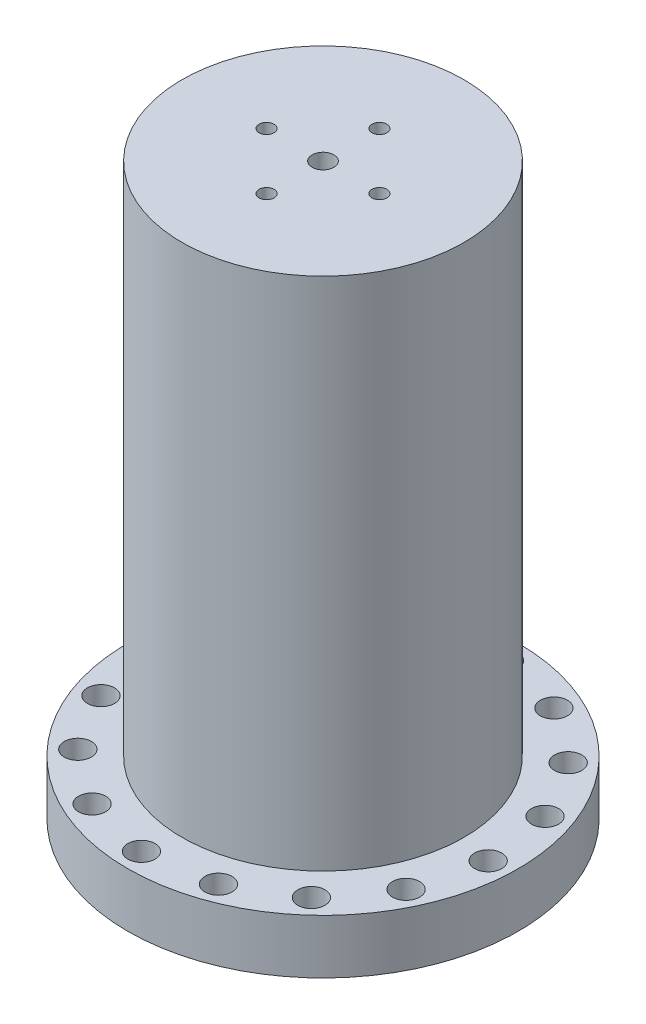
SolidWorks part; units mm, degrees
ref_plane "Front Plane" through (0, 0, 0) normal (0, 0, 1) x (1, 0, 0)
ref_plane "Top Plane" through (0, 0, 0) normal (0, 1, 0) x (1, 0, 0)
ref_plane "Right Plane" through (0, 0, 0) normal (1, 0, 0) x (0, 0, -1)
sketch "Sketch1" plane through (0, 0, 0) normal (0, 1, 0) x (1, 0, 0)
  circle A0 centre (0, 0) radius 45.72
extrude "Boss-Extrude1" add sketch "Sketch1" along normal blind 12.7
sketch "Sketch2" plane through (0, 12.7, 0) normal (0, 1, 0) x (1, 0, 0)
  circle A0 centre (0, 0) radius 33.02
extrude "Boss-Extrude2" add sketch "Sketch2" along normal blind 120.65
sketch "Sketch3" plane through (0, 0, 0) normal (0, -1, 0) x (1, 0, 0)
  circle A0 centre (0, 0) radius 25.4
extrude "Cut-Extrude1" cut sketch "Sketch3" against normal blind 128.27 contours A0
sketch "Sketch4" plane through (0, 133.35, 0) normal (0, 1, 0) x (1, 0, 0)
  circle A0 centre (0, 0) radius 2.54
extrude "Cut-Extrude2" cut sketch "Sketch4" against normal blind 128.27
sketch "Sketch5" plane through (0, 0, 0) normal (0, -1, 0) x (1, 0, 0)
  circle A0 centre (0, 0) radius 40.64
  circle A1 centre (-13.7597, -38.2398) radius 3.175
extrude "Cut-Extrude3" cut sketch "Sketch5" against normal blind 128.27 contours A1
ref_axis "Axis1" through (0, 128.27, 0) along (0, -1, 0)
sketch "Sketch6" plane through (0, 128.27, 0) normal (0, -1, 0) x (1, 0, 0)
  circle A0 centre (0, 0) radius 10.16
extrude "Cut-Extrude4" cut sketch "Sketch6" against normal blind 0.127
pattern_circular "CirPattern1" count 16 over 360 about axis through (0, 128.27, 0) along (0, -1, 0) of "Cut-Extrude3"
sketch "Sketch7" plane through (0, 128.27, 0) normal (0, -1, 0) x (1, 0, 0)
  circle A0 centre (0, 0) radius 13.208
  circle A1 centre (13.208, 0) radius 1.7526
  circle A2 centre (6.604, -11.4385) radius 1.7526
  circle A3 centre (-6.604, -11.4385) radius 1.7526
  circle A4 centre (-13.208, 0) radius 1.7526
  circle A5 centre (-6.604, 11.4385) radius 1.7526
  circle A6 centre (6.604, 11.4385) radius 1.7526
  point P17 (0, 0)
  dimension "D1" = 6
extrude "Cut-Extrude5" cut sketch "Sketch7" against normal through all contours A1
pattern_circular "CirPattern2" count 4 over 360 about axis through (0, 128.27, 0) along (0, -1, 0) of "Cut-Extrude5"
